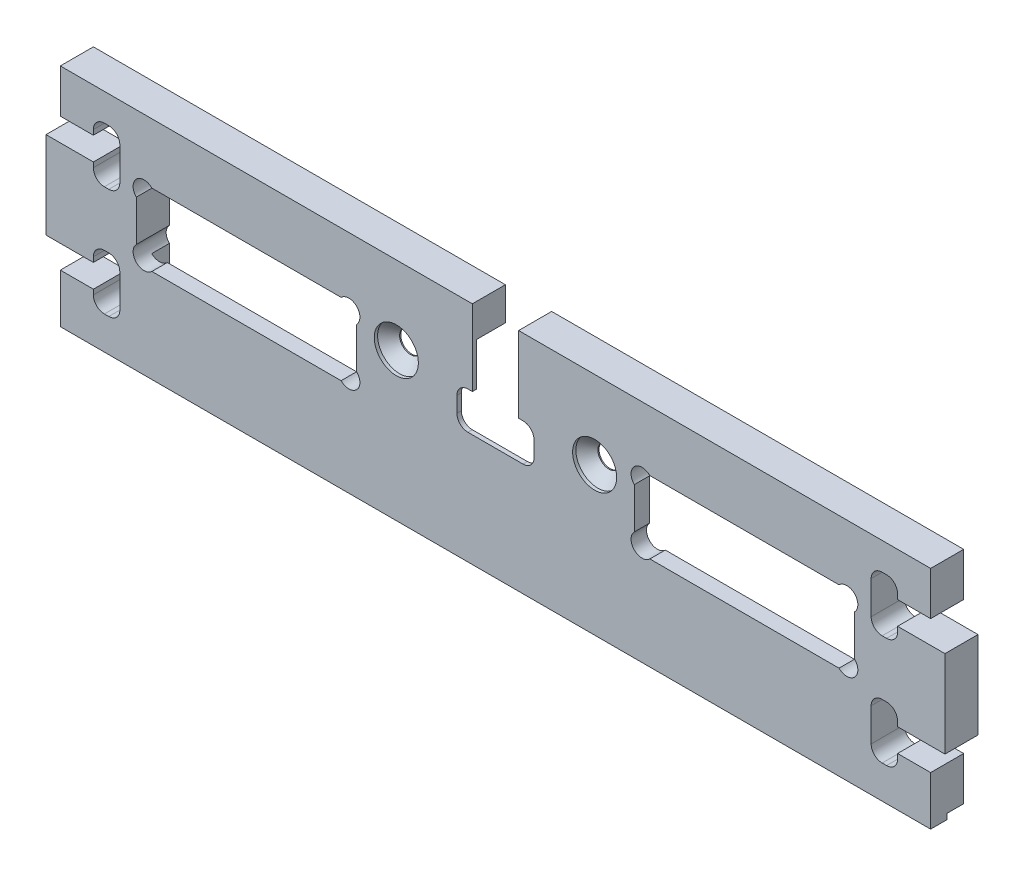
SolidWorks part; units mm, degrees
ref_plane "Front Plane" through (0, 0, 0) normal (0, 0, 1) x (1, 0, 0)
ref_plane "Top Plane" through (0, 0, 0) normal (0, 1, 0) x (1, 0, 0)
ref_plane "Right Plane" through (0, 0, 0) normal (1, 0, 0) x (0, 0, -1)
sketch "Sketch1" plane through (0, 0, 0) normal (0, 0, 1) x (1, 0, 0)
  line L0 (-39.5, 0) -> (39.5, 0) construction
  line L1 (-39.5, 10) -> (39.5, 10)
  line L2 (-39.5, 10) -> (-39.5, -10)
  line L3 (-39.5, -10) -> (39.5, -10)
  line L4 (39.5, 10) -> (39.5, -10)
  line L5 (-39.5, 10) -> (39.5, -10) construction
  line L6 (-39.5, -10) -> (39.5, 10) construction
  line L7 (0, 10) -> (0, -10) construction
  line L9 (-40.8, -3.95) -> (-39.5, -3.95)
  line L10 (-40.8, -3.95) -> (-40.8, 3.95)
  line L11 (-40.8, 3.95) -> (-39.5, 3.95)
  line L12 (-39.5, -3.95) -> (-39.5, 3.95)
  line L13 (-40.8, -3.95) -> (-39.5, 3.95) construction
  line L14 (-40.8, 3.95) -> (-39.5, -3.95) construction
  line L16 (40.8, 3.95) -> (39.5, 3.95)
  line L17 (40.8, -3.95) -> (40.8, 3.95)
  line L18 (40.8, -3.95) -> (39.5, -3.95)
  line L19 (-39.5, 5) -> (39.5, 5) construction
  line L20 (-35.3, 7.5) -> (-35.3, 2.5) construction
  line L21 (-36.5, 3.95) -> (-39.5, 3.95)
  line L22 (-36.5, 3.95) -> (-36.5, 6.05)
  line L23 (-36.5, 6.05) -> (-39.5, 6.05)
  line L24 (-39.5, 3.95) -> (-39.5, 6.05)
  line L25 (-36.5, 3.95) -> (-39.5, 6.05) construction
  line L26 (-36.5, 6.05) -> (-39.5, 3.95) construction
  line L27 (-34.1, 7.5) -> (-36.5, 7.5)
  line L28 (-34.1, 7.5) -> (-34.1, 2.5)
  line L29 (-34.1, 2.5) -> (-36.5, 2.5)
  line L30 (-36.5, 7.5) -> (-36.5, 2.5)
  line L31 (-34.1, 7.5) -> (-36.5, 2.5) construction
  line L32 (-34.1, 2.5) -> (-36.5, 7.5) construction
  line L33 (-34.1, -7.5) -> (-36.5, -7.5)
  line L34 (-34.1, -7.5) -> (-34.1, -2.5)
  line L35 (-34.1, -2.5) -> (-36.5, -2.5)
  line L36 (-36.5, -7.5) -> (-36.5, -2.5)
  line L37 (-36.5, -3.95) -> (-39.5, -3.95)
  line L38 (-36.5, -6.05) -> (-39.5, -6.05)
  line L39 (36.5, 3.95) -> (39.5, 3.95)
  line L40 (36.5, 6.05) -> (39.5, 6.05)
  line L41 (36.5, 7.5) -> (36.5, 2.5)
  line L42 (34.1, 7.5) -> (36.5, 7.5)
  line L43 (34.1, 7.5) -> (34.1, 2.5)
  line L44 (34.1, 2.5) -> (36.5, 2.5)
  line L45 (34.1, -2.5) -> (36.5, -2.5)
  line L46 (34.1, -7.5) -> (34.1, -2.5)
  line L47 (34.1, -7.5) -> (36.5, -7.5)
  line L48 (36.5, -7.5) -> (36.5, -2.5)
  line L49 (36.5, -6.05) -> (39.5, -6.05)
  line L50 (36.5, -3.95) -> (39.5, -3.95)
  point P0 (0, 0)
  point P10 (-40.15, 0)
  point P15 (-38, 5)
  point P35 (-35.3, 5)
  dimension "D1" = 79
  dimension "D2" = 20
  dimension "D4" = 1.3
  dimension "D7" = 5
  dimension "D8" = 2.1
  dimension "D9" = 3
  dimension "D10" = 2.4
  dimension "D11" = 5
extrude "Base shape" add sketch "Sketch1" along normal blind 3 contours L4 L1 L2 L3 | L9 L2 L11 L10 | L16 L4 L18 L17 region at (0, 0, 0) region at (-40.15, 0, 0) region at (40.15, 0, 0)
sketch "Sketch4" plane through (0, -10, 0) normal (0, -1, 0) x (1, 0, 0)
  line L0 (39.5, 3) -> (39.5, 0) construction
  line L1 (-39.5, 3) -> (39.5, 3)
  line L2 (-39.5, 3) -> (-39.5, 1.5)
  line L3 (-39.5, 1.5) -> (39.5, 1.5)
  line L4 (39.5, 3) -> (39.5, 1.5)
extrude "Floor lip" add sketch "Sketch4" along normal blind 0.5
sketch "Sketch6" plane through (0, 0, 0) normal (0, 0, -1) x (-1, 0, 0)
  line L0 (0, 0) -> (0, -10) construction
  line L1 (39.5, -10) -> (-39.5, -10) construction
  line L2 (-4, -10) -> (4, -10) construction
  line L3 (39.5, -10) -> (-39.5, -10) construction
  line L4 (-4, -9) -> (4, -9)
  line L5 (-4, -11) -> (4, -11)
  arc A0 (-4, -9) -> (-4, -11) centre (-4, -10) ccw
  arc A1 (4, -11) -> (4, -9) centre (4, -10) ccw
  point P9 (0, -10)
  dimension "D1" = 2
  dimension "D2" = 8
extrude "Nail cutout" cut sketch "Sketch6" against normal up to surface (1.5 mm away) up to face at (0, -10.25, 1.5)
sketch "Sketch3" plane through (-40.8, 0, 0) normal (-1, 0, 0) x (0, 0, 1)
  line L0 (0, 6.05) -> (3, 3.95) construction
  line L1 (0, 6.05) -> (3, 6.05)
  line L2 (0, 6.05) -> (0, 3.95)
  line L3 (0, 3.95) -> (3, 3.95)
  line L4 (3, 6.05) -> (3, 3.95)
  line L5 (0, -3.95) -> (3, -6.05) construction
  line L6 (0, -3.95) -> (3, -3.95)
  line L7 (0, -3.95) -> (0, -6.05)
  line L8 (0, -6.05) -> (3, -6.05)
  line L9 (3, -3.95) -> (3, -6.05)
  point P6 (1.5, 5)
  point P13 (1.5, -5)
ref_axis "Tap axis top" through (-53.7846, 5, 1.5) along (1, 0, 0)
ref_axis "Tap axis bottom" through (-54.2844, -5, 1.5) along (1, 0, 0)
fillet "Mill fillets" radius 1 16 edges at (36.5, -7.5, 1.5) (36.5, 2.5, 1.5) (34.1, 2.5, 1.5) (34.1, -7.5, 1.5) (36.5, -2.5, 1.5) (36.5, 7.5, 1.5) (34.1, -2.5, 1.5) (34.1, 7.5, 1.5) (-36.5, -2.5, 1.5) (-34.1, -2.5, 1.5) (-34.1, -7.5, 1.5) (-36.5, -7.5, 1.5) (-36.5, 2.5, 1.5) (-34.1, 2.5, 1.5) (-34.1, 7.5, 1.5) (-36.5, 7.5, 1.5)
sketch "Sketch8" [suppressed] plane through (0, 0, 3) normal (0, 0, 1) x (1, 0, 0)
  line L0 (-40.8, 0) -> (40.8, 0) construction
  line L1 (-40.8, -3.95) -> (-40.8, 3.95) construction
  line L2 (40.8, -3.95) -> (40.8, 3.95) construction
  line L4 (-24.5, 5.15) -> (24.5, 5.15)
  line L5 (-25.5, 4.15) -> (-25.5, -4.15)
  line L6 (-24.5, -5.15) -> (24.5, -5.15)
  line L7 (25.5, 4.15) -> (25.5, -4.15)
  line L8 (-25.5, 5.15) -> (25.5, -5.15) construction
  line L9 (-25.5, -5.15) -> (25.5, 5.15) construction
  arc A0 (24.5, -5.15) -> (25.5, -4.15) centre (24.5, -4.15) ccw
  arc A1 (24.5, 5.15) -> (25.5, 4.15) centre (24.5, 4.15) cw
  arc A2 (-25.5, -4.15) -> (-24.5, -5.15) centre (-24.5, -4.15) ccw
  arc A3 (-24.5, 5.15) -> (-25.5, 4.15) centre (-24.5, 4.15) ccw
  point P6 (0, 0)
  dimension "D3" = 1
  dimension "D1" = 51
  dimension "D2" = 10.3
extrude "Led strip pocket" [suppressed] cut sketch "Sketch8" against normal offset from surface (2.5 mm away) 0.5 up to face at (0, -0.6712, 0)
sketch "Sketch9" [suppressed] plane through (0, 0, 0.5) normal (0, 0, 1) x (1, 0, 0)
  line L0 (-19.5, 5.15) -> (-19.5, -5.15)
  line L1 (0, 5.15) -> (0, -5.15) construction
  line L2 (19.5, 5.15) -> (19.5, -5.15)
  line L3 (-25.5, -2.978) -> (25.5, -2.978) construction
  line L4 (25.5, -4.15) -> (25.5, 4.15)
  line L5 (24.5, 5.15) -> (-24.5, 5.15)
  line L6 (-25.5, 4.15) -> (-25.5, -4.15)
  line L7 (-24.5, -5.15) -> (24.5, -5.15)
  line L8 (25.5, -4.15) -> (25.5, 4.15)
  line L9 (24.5, 5.15) -> (-24.5, 5.15)
  line L10 (-25.5, 4.15) -> (-25.5, -4.15)
  line L11 (-24.5, -5.15) -> (24.5, -5.15)
  circle A0 centre (-12.7, -2.978) radius 1
  circle A1 centre (12.7, -2.978) radius 1
  arc A4 (24.5, -5.15) -> (25.5, -4.15) centre (24.5, -4.15) ccw
  arc A5 (25.5, 4.15) -> (24.5, 5.15) centre (24.5, 4.15) ccw
  arc A6 (-24.5, 5.15) -> (-25.5, 4.15) centre (-24.5, 4.15) ccw
  arc A7 (-25.5, -4.15) -> (-24.5, -5.15) centre (-24.5, -4.15) ccw
  arc A8 (24.5, -5.15) -> (25.5, -4.15) centre (24.5, -4.15) ccw
  arc A9 (25.5, 4.15) -> (24.5, 5.15) centre (24.5, 4.15) ccw
  arc A10 (-24.5, 5.15) -> (-25.5, 4.15) centre (-24.5, 4.15) ccw
  arc A11 (-25.5, -4.15) -> (-24.5, -5.15) centre (-24.5, -4.15) ccw
  arc M13 (24.5, -5.15) -> (25.5, -4.15) centre (24.5, -4.15) ccw
  line M14 (25.5, -4.15) -> (25.5, 4.15)
  arc M15 (25.5, 4.15) -> (24.5, 5.15) centre (24.5, 4.15) ccw
  line M16 (24.5, 5.15) -> (-24.5, 5.15)
  arc M17 (-24.5, 5.15) -> (-25.5, 4.15) centre (-24.5, 4.15) ccw
  line M18 (-25.5, 4.15) -> (-25.5, -4.15)
  arc M19 (-25.5, -4.15) -> (-24.5, -5.15) centre (-24.5, -4.15) ccw
  line M20 (-24.5, -5.15) -> (24.5, -5.15)
  dimension "D4" = 2
  dimension "D2" = 6
  dimension "D3" = 8.128
  dimension "D5" = 25.4
  dimension "D1" = 0
extrude "Led strip cuts" [suppressed] cut sketch "Sketch9" against normal up to next contours L0 M16 M17 M18 M19 M20 | L2 M16 M20 M13 M14 M15 | A0 | A1
fillet "Led strip cut fillets" [suppressed] radius 1
sketch "Sketch13" plane through (0, 0, 0) normal (0, 0, -1) x (-1, 0, 0)
  line L0 (0, 15.8648) -> (0, -21.9195) construction
  line L2 (-4.1, -5.7) -> (4.1, -5.7)
  line L3 (-5.1, -4.7) -> (-5.1, 6)
  line L4 (-4.1, 7) -> (4.1, 7)
  line L5 (5.1, -4.7) -> (5.1, 6)
  line L6 (-5.1, -5.7) -> (5.1, 7) construction
  line L7 (-5.1, 7) -> (5.1, -5.7) construction
  line L10 (39.5, 10) -> (-39.5, 10) construction
  arc A0 (-4.1, -5.7) -> (-5.1, -4.7) centre (-4.1, -4.7) cw
  arc A1 (4.1, -5.7) -> (5.1, -4.7) centre (4.1, -4.7) ccw
  arc A4 (5.1, 6) -> (4.1, 7) centre (4.1, 6) ccw
  arc A5 (-5.1, 6) -> (-4.1, 7) centre (-4.1, 6) cw
  point P1 (0, 0.65)
  dimension "D4" = 1
  dimension "D5" = 1
  dimension "D1" = 10.2
  dimension "D2" = 12.7
  dimension "D3" = 3
extrude "Bumper mount inner cut" cut sketch "Sketch13" against normal offset from surface (2.6 mm away) 0.4 up to face at (0, -0.0192, 3)
sketch "Sketch14" plane through (0, 0, 0) normal (0, 0, -1) x (-1, 0, 0)
  line L1 (0, 12.9528) -> (0, -14.0841) construction
  line L2 (4.1, 7) -> (-4.1, 7) construction
  line L3 (-4.1, -5.7) -> (4.1, -5.7) construction
  line L4 (-11.6, 7) -> (11.6, 7)
  line L5 (-12.6, 6) -> (-12.6, -4.7)
  line L6 (-11.6, -5.7) -> (11.6, -5.7)
  line L7 (12.6, 6) -> (12.6, -4.7)
  line L8 (-12.6, 7) -> (12.6, -5.7) construction
  line L9 (-12.6, -5.7) -> (12.6, 7) construction
  arc A1 (11.6, -5.7) -> (12.6, -4.7) centre (11.6, -4.7) ccw
  arc A2 (-12.6, -4.7) -> (-11.6, -5.7) centre (-11.6, -4.7) ccw
  arc A3 (11.6, 7) -> (12.6, 6) centre (11.6, 6) cw
  arc A4 (-12.6, 6) -> (-11.6, 7) centre (-11.6, 6) cw
  point P6 (0, 0.65)
  dimension "D2" = 1
  dimension "D3" = 1
  dimension "D1" = 25.2
extrude "Bumper mount outer cut" cut sketch "Sketch14" against normal blind 1.6
sketch "Sketch15" plane through (0, 0, 1.6) normal (0, 0, -1) x (-1, 0, 0)
  line L0 (-12.6, 2.9) -> (12.6, 2.9) construction
  line L3 (0, 16.4744) -> (0, -20.0474) construction
  line L7 (-12.6, 6) -> (-12.6, -4.7) construction
  line L8 (12.6, -4.7) -> (12.6, 6) construction
  line L11 (-4.1, 7) -> (-11.6, 7) construction
  circle A0 centre (-9, 2.9) radius 1
  circle A1 centre (9, 2.9) radius 1
  dimension "D1" = 18
  dimension "D2" = 2
  dimension "D3" = 4.1
extrude "Bumper mount screw holes" cut sketch "Sketch15" against normal up to next
sketch "Sketch16" plane through (0, 0, 2.6) normal (0, 0, -1) x (-1, 0, 0)
  line L0 (-5.1, 1.4) -> (5.1, 1.4) construction
  line L3 (0, 7) -> (0, -4.2) construction
  line L4 (-2.5, 3.1) -> (2.5, 3.1)
  line L5 (-3.5, 2.1) -> (-3.5, 0.7)
  line L6 (-2.5, -0.3) -> (2.5, -0.3)
  line L7 (3.5, 2.1) -> (3.5, 0.7)
  line L8 (-3.5, 3.1) -> (3.5, -0.3) construction
  line L9 (-3.5, -0.3) -> (3.5, 3.1) construction
  line L11 (-5.1, 6) -> (-5.1, -4.7) construction
  line L13 (4.1, 7) -> (-4.1, 7) construction
  arc A0 (2.5, -0.3) -> (3.5, 0.7) centre (2.5, 0.7) ccw
  arc A1 (-3.5, 0.7) -> (-2.5, -0.3) centre (-2.5, 0.7) ccw
  arc A2 (-2.5, 3.1) -> (-3.5, 2.1) centre (-2.5, 2.1) ccw
  arc A3 (2.5, 3.1) -> (3.5, 2.1) centre (2.5, 2.1) cw
  point P6 (0, 1.4)
  dimension "D3" = 1
  dimension "D1" = 7
  dimension "D2" = 3.4
  dimension "D4" = 11.2
extrude "Bumper body cut" cut sketch "Sketch16" against normal up to next
hole_wizard "Bumper screw countersunks" positions "Sketch17" profile "Sketch18" countersink size "M2" standard "ANSI Metric" end condition through all
sketch "Sketch17" plane through (0, 0, 3) normal (0, 0, 1) x (1, 0, 0)
  point P0 (9, 2.9)
  point P3 (-9, 2.9)
sketch "Sketch18" plane through (9, 2.9, 3) normal (1, 0, 0) x (0, -1, 0)
  line L0 (0, 0) -> (0, 3)
  line L1 (0, 3) -> (1, 3)
  line L2 (1, 3) -> (1, 1.3)
  line L3 (1, 1.3) -> (2, 0.3)
  line L4 (2, 0.3) -> (2, 0)
  line L6 (2, 0) -> (0, 0)
  line L7 (-1, 1.3) -> (-2, 0.3) construction
  line L11 (0, -6.35) -> (0, 107.95) construction
  dimension "Thru Hole Dia." = 2
  dimension "Thru Hole Depth" = 3
  dimension "C'Sink Dia." = 4
  dimension "C'Sink Angle" = 90
  dimension "Head Clearance" = 0.3
sketch "Sketch19" plane through (0, 0, 0) normal (0, 0, -1) x (-1, 0, 0)
  line L0 (0, 15.6498) -> (0, -12.9575) construction
  line L1 (39.5, 10) -> (-39.5, 10) construction
  line L2 (-2.1, 3.1) -> (2.1, 3.1)
  line L3 (-2.1, 3.1) -> (-2.1, 10)
  line L4 (-2.1, 10) -> (2.1, 10)
  line L5 (2.1, 3.1) -> (2.1, 10)
  line L6 (-2.1, 3.1) -> (2.1, 10) construction
  line L7 (-2.1, 10) -> (2.1, 3.1) construction
  line L8 (2.5, 3.1) -> (-2.5, 3.1) construction
  point P1 (0, 6.55)
  dimension "D1" = 4.2
extrude "Bumper insertion cut" cut sketch "Sketch19" against normal up to next
sketch "Sketch20" plane through (0, 0, 0) normal (0, 0, -1) x (-1, 0, 0)
  line L0 (-12.6, 6) -> (-12.6, -4.7) construction
  line L1 (-12.6, 4.55) -> (-32.6, 4.55)
  line L2 (-12.6, 4.55) -> (-12.6, -2)
  line L3 (-12.6, -2) -> (-32.6, -2)
  line L4 (-32.6, 4.55) -> (-32.6, -2)
  line L5 (-2.1, 10) -> (-39.5, 10) construction
  line L6 (-12.6, 4.55) -> (-19.15, -2) construction
  line L7 (-22.6, 4.55) -> (-22.6, -2) construction
  line L8 (-32.6, 1.275) -> (-12.6, 1.275) construction
  line L9 (0, 16.176) -> (0, -15.99) construction
  line L10 (12.6, 4.55) -> (12.6, -2)
  line L11 (12.6, -2) -> (32.6, -2)
  line L12 (32.6, 4.55) -> (32.6, -2)
  line L13 (12.6, 4.55) -> (32.6, 4.55)
  circle A0 centre (-13.3071, 3.8429) radius 1
  circle A1 centre (-31.8929, 3.8429) radius 1
  circle A2 centre (-13.3071, -1.2929) radius 1
  circle A3 centre (-31.8929, -1.2929) radius 1
  circle A4 centre (13.3071, 3.8429) radius 1
  circle A5 centre (13.3071, -1.2929) radius 1
  circle A6 centre (31.8929, -1.2929) radius 1
  circle A7 centre (31.8929, 3.8429) radius 1
  dimension "D5" = 2
  dimension "D1" = 20
  dimension "D2" = 5.45
  dimension "D3" = 6.55
  dimension "D4" = 45
extrude "Bumper switches cut" cut sketch "Sketch20" against normal up to next contours L1 L4 L3 L2 | A1 | A3 | A0 | A2 | L13 L12 L11 L10 | A4 | A5 | A6 | A7
sketch "Sketch21" plane through (0, 0, 0) normal (0, 0, -1) x (-1, 0, 0)
  line L0 (-14.0142, -2) -> (-31.1858, -2) construction
  line L1 (-32.6, -2) -> (-12.6, -2)
  line L2 (-32.6, -2) -> (-32.6, -5.7)
  line L3 (-32.6, -5.7) -> (-12.6, -5.7)
  line L4 (-12.6, -2) -> (-12.6, -5.7)
  line L5 (-12.6, -2) -> (-12.6, -4.7) construction
  line L6 (-11.6, -5.7) -> (-4.1, -5.7) construction
  line L7 (-32.6, 3.1358) -> (-32.6, -0.5858) construction
  line L8 (-12.6, -5.7) -> (-11.6, -5.7)
  line L9 (-32.6, -5.7) -> (-28.9, -2) construction
  line L10 (0, 14.2019) -> (0, -15.3745) construction
  line L11 (12.6, -5.7) -> (11.6, -5.7)
  line L12 (12.6, -2) -> (12.6, -5.7)
  line L13 (32.6, -2) -> (12.6, -2)
  line L14 (32.6, -2) -> (32.6, -5.7)
  line L15 (32.6, -5.7) -> (12.6, -5.7)
  arc A0 (-12.6, -4.7) -> (-11.6, -5.7) centre (-11.6, -4.7) ccw construction
  arc A1 (-12.6, -4.7) -> (-11.6, -5.7) centre (-11.6, -4.7) ccw
  circle A2 centre (-31.8929, -4.9929) radius 1
  arc A3 (-32.6, -0.5858) -> (-31.1858, -2) centre (-31.8929, -1.2929) ccw construction
  circle A4 centre (31.8929, -4.9929) radius 1
  arc A5 (12.6, -4.7) -> (11.6, -5.7) centre (11.6, -4.7) cw
  dimension "D1" = 45
extrude "Bumper switch mounts cut" cut sketch "Sketch21" against normal up to surface (1.6 mm away) contours A1 L4 L8 | L12 A5 L11 | L4 L1 L2 L3 | A2 | L12 L13 L14 L15 | A4 region at (12.3766, -5.4766, 0) region at (-12.3766, -5.4766, 0) up to face at (-8, 2.9, 1.6)
sketch "Outer coordinate system sketch" plane through (0, 0, 3) normal (0, 0, 1) x (1, 0, 0)
  line L0 (-40.8, -3.95) -> (-40.8, -10.5) construction
  line L1 (-40.8, -10.5) -> (-39.5, -10.5) construction
  point P6 (-40.8, -10.5)
sketch "Inner coordinate system sketch" plane through (0, 0, 0) normal (0, 0, 1) x (1, 0, 0)
  point P0 (-9, 2.9)
  point P1 (0, 0)
